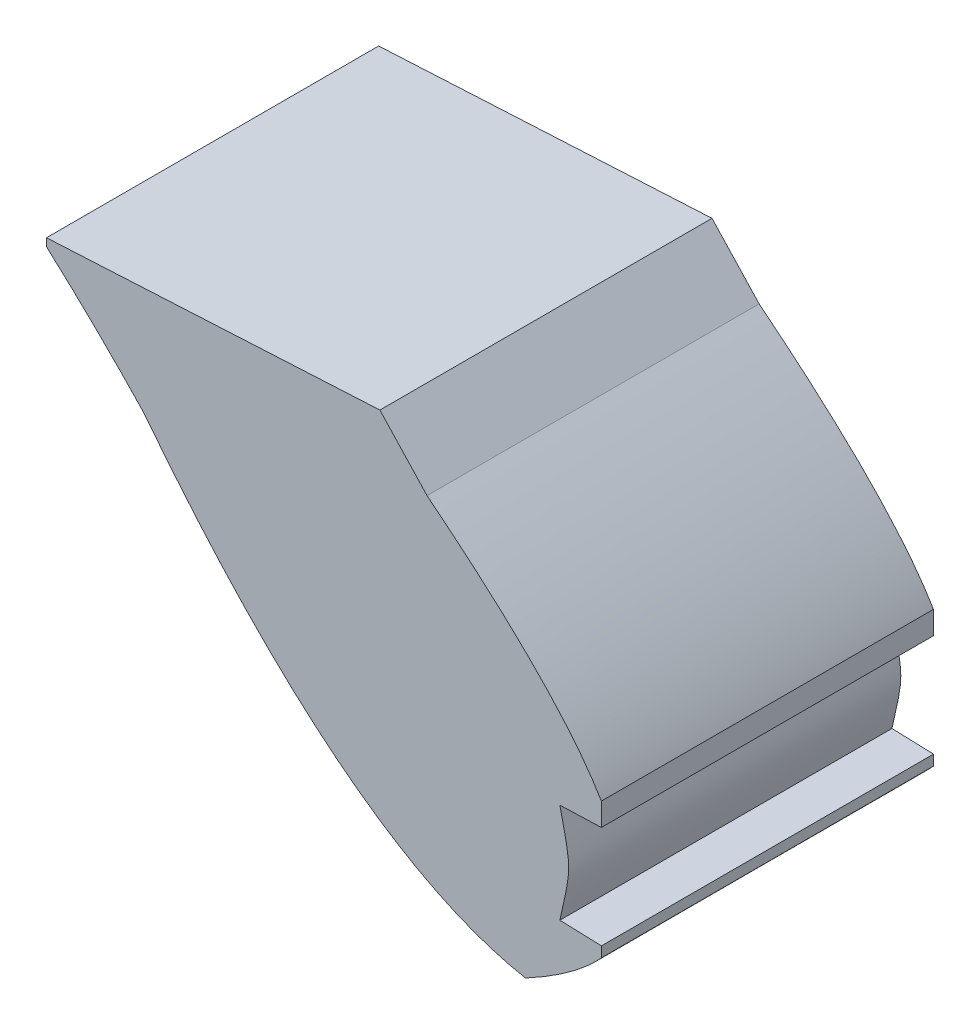
SolidWorks part; units mm, degrees
ref_plane "Alzado" through (0, 0, 0) normal (0, 0, 1) x (1, 0, 0)
ref_plane "Planta" through (0, 0, 0) normal (0, 1, 0) x (1, 0, 0)
ref_plane "Vista lateral" through (0, 0, 0) normal (1, 0, 0) x (0, 0, -1)
sketch "Croquis1" plane through (0, 0, 0) normal (0, 0, 1) x (1, 0, 0)
  line L0 (-8.9818, 12.6082) -> (-23.0359, 11.8716) construction
  line L1 (-8.9818, 12.6082) -> (-23.0359, 11.8716)
  line L2 (-8.9818, 12.6082) -> (-23.0359, 11.8716) construction
  line L4 (-8.9818, 12.6082) -> (-23.0359, 11.8716)
  line L6 (-1.3949, 1.9763) -> (0.3551, 2.2848) construction
  line L7 (-1.3949, 1.9763) -> (0.3551, 2.2848)
  line L8 (0.3551, 2.2848) -> (0.3551, 2.8423) construction
  line L9 (0.3551, 2.2848) -> (0.3551, 3.0015)
  line L10 (0.3551, -2.2848) -> (-1.3949, -2.2237) construction
  line L11 (0.3551, -2.2848) -> (-1.3949, -2.2237)
  line L12 (0.3551, 2.2848) -> (0.3551, -2.2848) construction
  line L13 (0.3551, -2.2848) -> (0.3551, -2.7233)
  line L14 (-8.9818, 12.6082) -> (-6.9949, 10.4774)
  line L15 (-23.0359, 11.5401) -> (-23.0359, 11.8716) construction
  line L16 (-23.0359, 11.5401) -> (-23.0359, 11.8716)
  arc A0 (-18.9452, 7.5409) -> (-23.0359, 11.5401) centre (-69.8841, -40.4718) ccw construction
  arc A1 (-18.9452, 7.5409) -> (-23.0359, 11.5401) centre (-69.8841, -40.4718) ccw
  spline S1 degree 2 poles (-828.7061, 3922.2202) (545.889, -3962.7836) (-262.0834, 3982.5902) knots 0.462185 0.462185 0.462185 0.537731 0.537731 0.537731 weights 1 1 1 only from (-18.9452, 7.5409) to (-2.8466, -5.0591) construction
  spline S2 degree 2 poles (-18.9452, 7.5409) (-10.215, -3.6976) (-2.8466, -5.0591) knots 0.497667 0.497667 0.497667 0.499554 0.499554 0.499554 weights 1 1 1
  spline S3 degree 2 poles (-3804.8689, 1232.5771) (3762.9122, -1369.6643) (-3716.5752, 1504.852) knots 0.462212 0.462212 0.462212 0.537836 0.537836 0.537836 weights 1 1 1 only from (0.3551, 3.0015) to (-6.9949, 10.4774) construction
  spline S4 degree 2 poles (0.3551, 3.0015) (-1.4487, 6.0584) (-6.9949, 10.4774) knots 0.500821 0.500821 0.500821 0.502013 0.502013 0.502013 weights 1 1 1
  spline S5 degree 2 poles (-1.3949, -2.2237) (-0.9075, -0.1237) (-1.3949, 1.9763) knots 0 0 0 1 1 1 weights 1 3.231801 1 construction
  spline S6 degree 2 poles (-1.3949, -2.2237) (-0.9075, -0.1237) (-1.3949, 1.9763) knots 0 0 0 1 1 1 weights 1 3.231801 1
  spline S7 degree 2 poles (-3997.263, 185.0077) (3984.2333, -348.7483) (-3965.0625, 511.2595) knots 0.462205 0.462205 0.462205 0.537778 0.537778 0.537778 weights 1 1 1 only from (-2.8466, -5.0591) to (0.3551, -2.7233) construction
  spline S8 degree 2 poles (-2.8466, -5.0591) (-0.7424, -3.9352) (0.3551, -2.7233) knots 0.498812 0.498812 0.498812 0.499413 0.499413 0.499413 weights 1 1 1
extrude "Saliente-Extruir1" add sketch "Croquis1" along normal mid plane 14 contours S2 S8 L13 L11 S6 L7 L9 S4 L14 L1 L16 A1 region at (-9.5529, 4.8585, 0)
sketch "Croquis3" plane through (0, 0, 0) normal (0, 0, 1) x (1, 0, 0)
  line L0 (-6.742, 0) -> (0, 0) construction
  line L1 (-1.8181, 2) -> (-1.7771, 2.0103) construction
  line L3 (-1.8181, 2) -> (-0.1689, 2.4155) construction
  line L4 (-1.8181, 2) -> (0.3551, 3.0015)
  line L5 (0.3551, 3.0015) -> (0.3551, 0)
  line L6 (-1.9135, -2.1825) -> (0.3551, -2.2848)
  line L7 (0.3551, -2.2848) -> (0.3551, 0)
  parabola Q0 (-1.9135, -2.1825) -> (-1.8181, 2) focus (-3.3181, 0) apex (-1.3181, 0)
  dimension "D1" = 2
  dimension "D2" = 2
extrude "Cortar-Extruir1" [suppressed] cut sketch "Croquis3" against normal through all both and the other way through all
sketch "Croquis4" plane through (0, 0, 0) normal (0, 0, 1) x (1, 0, 0)
  line L0 (-1.3949, 1.9763) -> (0.3551, 2.2848) construction
  line L1 (-1.3949, 1.9763) -> (0.3551, 2.2848)
  line L2 (0.3551, 2.2848) -> (0.3551, 3.0015) construction
  line L3 (0.3551, 2.0374) -> (0.3551, 2.2848)
  line L4 (-1.3949, 1.9763) -> (0.3551, 2.0374)
  line L5 (0, 0) -> (-3.4665, 0) construction
  dimension "D1" = 2
extrude "Saliente-Extruir2" add sketch "Croquis4" along normal through all and the other way through all
sketch "Croquis7" plane through (0, 0, 0) normal (0, 0, 1) x (1, 0, 0)
  line L0 (0, 0) -> (-15.3945, 3.3171) construction
  line L1 (-17.3963, 18.9371) -> (-15.3945, 3.3171) construction
  line L2 (-15.3945, 3.3171) -> (-9.9316, -2.6296) construction
  line L3 (-15.3945, 3.3171) -> (-10.2385, 8.0535) construction
  line L4 (-17.3963, 18.9371) -> (-16.5429, 12.2783) construction
  line L5 (0, 0) -> (-1.3461, -2.2254) construction
  line L6 (-69.8841, 29.5282) -> (-81.9382, 42.5765) construction
  line L7 (-69.8841, 29.5282) -> (-20.9497, 29.5282) construction
  line L8 (-17.8101, 13.1658) -> (-25.5429, 13.1658)
  line L9 (-18.2059, 7.0951) -> (-21.9246, 11.9299) construction
  line L10 (0.3551, -2.5) -> (-2.4497, -2.0473)
  line L11 (-1.3461, -2.2254) -> (-2.0075, -3.6222) construction
  line L12 (-1.3461, -2.2254) -> (-1.4547, -2.8987) construction
  line L13 (-1.3461, -2.2254) -> (-1.2286, -1.4976) construction
  line L14 (0.3551, -2.2848) -> (0.3551, -2.7233) construction
  line L15 (0.3551, -2.2848) -> (-1.3949, -2.2237) construction
  line L16 (-2.0075, -3.6222) -> (-3.0629, -5.8512) construction
  line L17 (-2.6331, -4.9434) -> (-3.7044, -5.5324) construction
  line L18 (-2.6331, -4.9434) -> (-3.2248, -3.867) construction
  line L19 (-2.6331, -4.9434) -> (-2.2174, -6.1341) construction
  line L20 (-4.0838, -4.7637) -> (-1.6363, -5.0668) construction
  line L21 (-4.0838, -4.7637) -> (-0.036, -5.9454) construction
  line L22 (-4.0838, -4.7637) -> (-3.7621, -3.6616) construction
  line L23 (-4.0838, -4.7637) -> (-6.31, -3.7023) construction
  line L24 (-6.31, -3.7023) -> (-8.69, -2.5677) construction
  line L25 (-8.69, -2.5677) -> (-6.8421, -3.7725) construction
  line L26 (-8.69, -2.5677) -> (-7.9481, -1.4297) construction
  line L27 (-10.6884, -0.8477) -> (-8.69, -2.5677) construction
  line L28 (-10.6884, -0.8477) -> (-14.8546, 2.738) construction
  line L29 (-14.8546, 2.738) -> (-14.5337, 2.3989) construction
  line L30 (-14.8546, 2.738) -> (-14.6199, 2.9602) construction
  line L31 (-18.2059, 7.0951) -> (-14.8546, 2.738) construction
  line L32 (-8.9818, 12.6082) -> (-23.0359, 11.8716) construction
  line L33 (-8.9818, 12.6082) -> (-23.0359, 11.8716)
  line L34 (-21.9246, 11.9299) -> (-21.9826, 13.0367) construction
  line L35 (-21.9246, 11.9299) -> (-23.4156, 13.0367) construction
  arc A0 (-18.9452, 7.5409) -> (-23.0359, 11.5401) centre (-69.8841, -40.4718) ccw construction
  spline S0 degree 2 poles (-654.4568, 2937.5195) (409.3679, -2972.9237) (-163.476, 2987.5518) knots 0.467242 0.467242 0.467242 0.532662 0.532662 0.532662 weights 1 1 1 only from (-18.9452, 7.5409) to (-2.8466, -5.0591) construction
  spline S1 degree 2 poles (-18.6263, 7.1332) (-10.0803, -3.7225) (-2.8466, -5.0591) knots 0.497702 0.497702 0.497702 0.499554 0.499554 0.499554 weights 1 1 1 construction
  spline S3 degree 2 poles (-2999.4042, 119.7504) (2988.2948, -261.6206) (-2971.0465, 402.239) knots 0.467267 0.467267 0.467267 0.532713 0.532713 0.532713 weights 1 1 1 only from (-2.8466, -5.0591) to (0.3551, -2.7233) construction
  spline S4 degree 2 poles (-2.8466, -5.0591) (-2.7385, -5.0013) (-2.6331, -4.9434) knots 0.498812 0.498812 0.498812 0.498843 0.498843 0.498843 weights 1 1 1
  dimension "D1" = 2.5
  dimension "D2" = 22
  dimension "D3" = 16.17
  dimension "D4" = 54.138
  dimension "D5" = 34.566
  dimension "D6" = 50.413
sketch "Croquis6" plane through (0, 0, 0) normal (1, 0, 0) x (0, 0, -1)
  line L0 (7, 12.6082) -> (7, 10.4774) construction
  line L1 (7, 12.6082) -> (7, -5.0591)
  line L2 (-7, 12.6082) -> (-7, 10.4774) construction
  line L3 (-7, 12.6082) -> (-7, -5.0591)
  line L4 (-7, -5.0591) -> (7, -5.0591) construction
  line L5 (-7, -5.0591) -> (12.4533, -5.0591)
  line L6 (7, 12.6082) -> (5, -5.0591)
  line L7 (-7, 12.6082) -> (12.4533, -5.0591)
  line L8 (5, -5.0591) -> (7, -5.0591)
  dimension "D1" = 19.4533
  dimension "D2" = 2
extrude "Cortar-Extruir2" cut sketch "Croquis6" against normal through all and the other way through all rebuild error yes
